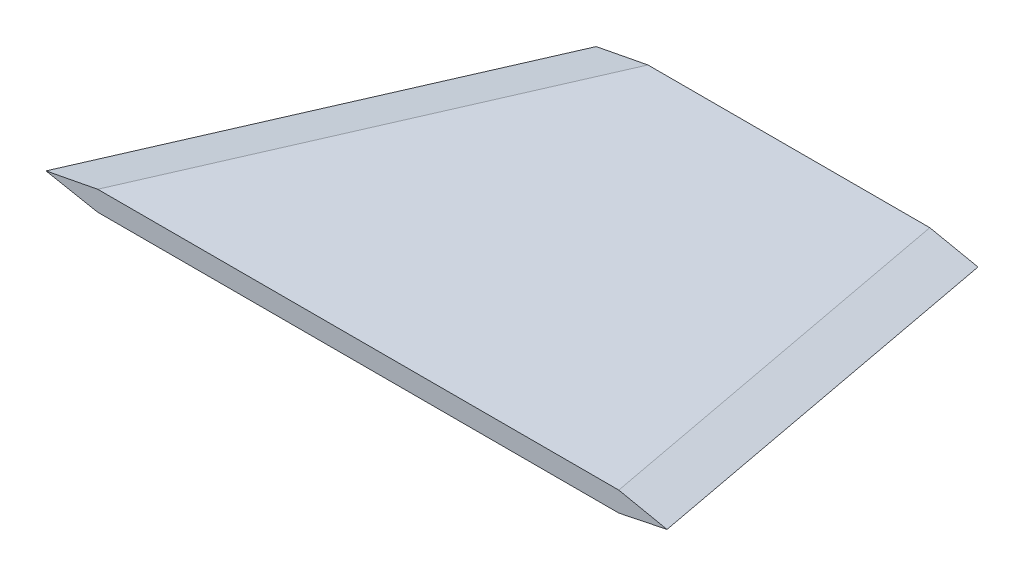
SolidWorks part; units mm, degrees
material "Thornel VCB-20 Carbon Cloth"
ref_plane "Front Plane" through (0, 0, 0) normal (0, 0, 1) x (1, 0, 0)
ref_plane "Top Plane" through (0, 0, 0) normal (0, 1, 0) x (1, 0, 0)
ref_plane "Right Plane" through (0, 0, 0) normal (1, 0, 0) x (0, 0, -1)
sketch "Sketch1" plane through (0, 0, 0) normal (0, 1, 0) x (1, 0, 0)
  line L0 (0, 0) -> (165.1, 0)
  line L1 (165.1, 0) -> (146.05, 101.6)
  line L2 (146.05, 101.6) -> (44.45, 101.6)
  line L3 (44.45, 101.6) -> (0, 0)
  dimension "D1" = 165.1
  dimension "D2" = 101.6
  dimension "D3" = 44.45
  dimension "D4" = 101.6
extrude "Boss-Extrude1" add sketch "Sketch1" along normal blind 5.2832
chamfer "Chamfer1" distance 2.667 distance2 12.7 2 edges at (22.225, 0, -50.8) (22.225, 5.2832, -50.8) first distance on face at (22.225, 2.6416, -50.8)
chamfer "Chamfer2" distance 12.7 distance2 2.667 1 edges at (155.575, 0, -50.8) first distance on face at (95.8311, 0, -50.8)
chamfer "Chamfer3" distance 2.667 distance2 12.7 1 edges at (155.575, 5.2832, -50.8) first distance on face at (155.575, 3.9751, -50.8)
